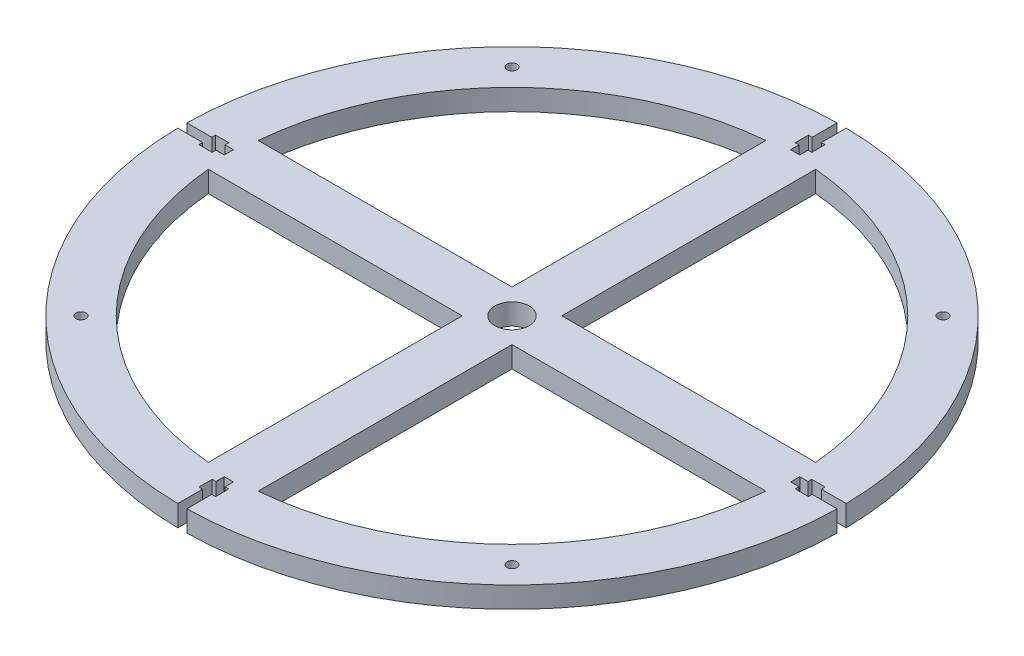
SolidWorks part; units mm, degrees
material "6061 Alloy"
ref_plane "Front Plane" through (0, 0, 0) normal (0, 0, 1) x (1, 0, 0)
ref_plane "Top Plane" through (0, 0, 0) normal (0, 1, 0) x (1, 0, 0)
ref_plane "Right Plane" through (0, 0, 0) normal (1, 0, 0) x (0, 0, -1)
sketch "Sketch1" plane through (0, 0, 0) normal (0, 1, 0) x (1, 0, 0)
  line L0 (0, -99.238) -> (0, 99.238) construction
  line L1 (-99.238, 0) -> (99.238, 0) construction
  line L2 (-98.9542, -7.5) -> (98.9542, -7.5)
  line L3 (7.5, -98.9542) -> (7.5, 98.9542)
  line L4 (-98.9542, 7.5) -> (98.9542, 7.5)
  line L5 (-7.5, -98.9542) -> (-7.5, 98.9542)
  line L6 (-7.5, -99.238) -> (-7.5, 99.238) construction
  line L7 (7.5, -99.238) -> (7.5, 99.238) construction
  line L8 (-99.238, -7.5) -> (99.238, -7.5) construction
  line L9 (-99.238, 7.5) -> (99.238, 7.5) construction
  circle A0 centre (0, 0) radius 100 construction
  circle A1 centre (0, 0) radius 99.238
  circle A2 centre (0, 0) radius 84.238
  point P7 (0, 0)
  point P11 (0, 0)
  dimension "D1" = 200
  dimension "D2" = 0.762
  dimension "D3" = 15
  dimension "D4" = 7.5
  dimension "D5" = 7.5
extrude "Boss-Extrude1" add sketch "Sketch1" along normal mid plane 6.35 contours A2 L2 A1 L5 | A2 L4 A1 L2 | A2 L5 A1 L4 | A2 L3 A1 L5 | A2 L4 A1 L3 | A2 L2 A1 L4 | A2 L3 A1 L2 | A2 L5 A1 L3 | L5 A2 L3 L2 | L4 A2 L2 L5 | L3 A2 L5 L4 | L2 A2 L4 L3 | L5 L2 L3 L4 region at (-91.6349, 0, 0) region at (-59.7933, 0, 59.7933) region at (-45.8134, 0, 0) region at (-59.7933, 0, -59.7933) region at (0, 0, 91.6349) region at (0, 0, 0) region at (0, 0, 45.8134) region at (0, 0, -91.6349) region at (59.7933, 0, 59.7933) region at (45.8134, 0, 0) region at (0, 0, -45.8134) region at (59.7933, 0, -59.7933) region at (91.6349, 0, 0)
sketch "Sketch2" plane through (0, 0, 0) normal (0, 1, 0) x (1, 0, 0)
  line L0 (-1.375, 85.238) -> (-1.375, 99.238)
  line L1 (-1.375, 85.238) -> (1.375, 85.238)
  line L2 (-1.375, 99.238) -> (1.375, 99.238)
  line L3 (1.375, 85.238) -> (1.375, 99.238)
  line L4 (-1.375, 85.238) -> (1.375, 99.238) construction
  line L5 (-1.375, 99.238) -> (1.375, 85.238) construction
  line L6 (-2.5, 87.738) -> (-2.5, 91.738)
  line L7 (-2.5, 87.738) -> (2.5, 87.738)
  line L8 (-2.5, 91.738) -> (2.5, 91.738)
  line L9 (2.5, 87.738) -> (2.5, 91.738)
  line L10 (-2.5, 87.738) -> (2.5, 91.738) construction
  line L11 (-2.5, 91.738) -> (2.5, 87.738) construction
  line L12 (0, -1000) -> (0, 49000) construction
  line L13 (-1000, 0) -> (49000, 0) construction
  circle A0 centre (0, 0) radius 99.238 construction
  point P1 (0, 92.238)
  point P2 (0, 89.738)
  dimension "D1" = 2.75
  dimension "D2" = 14
  dimension "D3" = 4
  dimension "D4" = 5
  dimension "D5" = 2.5
extrude "Cut-Extrude1" cut sketch "Sketch2" against normal through all both and the other way through all contours L7 L0 L1 L3 | L8 L0 L7 L3 | L7 L9 L8 L3 | L0 L8 L3 L2 | L8 L6 L7 L0 region at (0, 0, -86.488) region at (-1.9375, 0, -89.738) region at (0, 0, -89.738) region at (0, 0, -95.488) region at (1.9375, 0, -89.738)
pattern_circular "CirPattern1" count 4 over 360 about axis through (0, 3.175, 0) along (0, 1, 0) of "Cut-Extrude1"
hole_wizard "Ø3.0 (3) Diameter Hole1" positions "Sketch3" profile "Sketch4" hole size "Ø3.0" standard "ANSI Metric" end condition up to next
sketch "Sketch3" plane through (0, 3.175, 0) normal (0, 1, 0) x (1, 0, 0)
  line L0 (-70.1719, -70.1719) -> (70.1719, 70.1719) construction
  line L2 (-70.1719, 70.1719) -> (70.1719, -70.1719) construction
  line L4 (70.1719, 70.1719) -> (59.5653, 59.5653)
  line L6 (70.1719, -70.1719) -> (59.5653, -59.5653)
  line L8 (-70.1719, -70.1719) -> (-59.5653, -59.5653)
  line L10 (-70.1719, 70.1719) -> (-59.5653, 59.5653)
  arc A0 (99.2285, 1.375) -> (1.375, 99.2285) centre (0, 0) ccw construction
  arc A1 (1.375, -99.2285) -> (99.2285, -1.375) centre (0, 0) ccw construction
  arc A2 (83.9035, 7.5) -> (7.5, 83.9035) centre (0, 0) ccw construction
  arc A3 (7.5, -83.9035) -> (83.9035, -7.5) centre (0, 0) ccw construction
  arc A4 (-83.9035, -7.5) -> (-7.5, -83.9035) centre (0, 0) ccw construction
  arc A5 (-7.5, 83.9035) -> (-83.9035, 7.5) centre (0, 0) ccw construction
  point P107 (0, 0)
  point P324 (0, 0)
  point P360 (-64.8686, 64.8686)
  point P362 (64.8686, 64.8686)
  point P364 (64.8686, -64.8686)
  point P366 (-64.8686, -64.8686)
sketch "Sketch4" plane through (-64.8686, 3.175, 64.8686) normal (1, 0, 0) x (0, 0, 1)
  line L0 (0, 0) -> (0, 6.35)
  line L1 (0, 6.35) -> (1.5, 6.35)
  line L2 (1.5, 6.35) -> (1.5, 0)
  line L5 (1.5, 0) -> (0, 0)
  line L11 (0, -6.35) -> (0, 107.95) construction
  dimension "Thru Hole Dia." = 3
  dimension "Thru Hole Depth" = 6.35
hole_wizard "3/8 Clearance Hole1" positions "Sketch5" profile "Sketch6" hole size "3/8" standard "ANSI Inch" end condition up to next
sketch "Sketch5" plane through (0, 3.175, 0) normal (0, 1, 0) x (1, 0, 0)
  point P0 (0, 0)
sketch "Sketch6" plane through (0, 3.175, 0) normal (1, 0, 0) x (0, 0, 1)
  line L0 (0, 0) -> (0, 6.35)
  line L1 (0, 6.35) -> (5.1587, 6.35)
  line L2 (5.1587, 6.35) -> (5.1587, 0)
  line L5 (5.1587, 0) -> (0, 0)
  line L11 (0, -6.35) -> (0, 107.95) construction
  dimension "Thru Hole Dia." = 10.3175
  dimension "Thru Hole Depth" = 6.35
